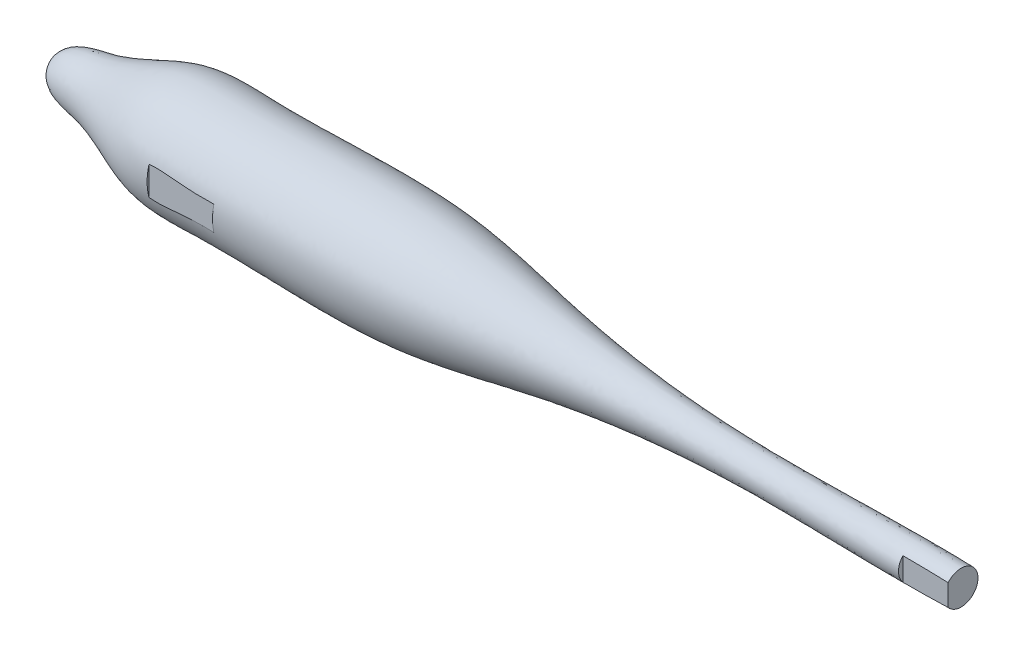
SolidWorks part; units mm, degrees
ref_plane "Front Plane" through (0, 0, 0) normal (0, 0, 1) x (1, 0, 0)
ref_plane "Top Plane" through (0, 0, 0) normal (0, 1, 0) x (1, 0, 0)
ref_plane "Right Plane" through (0, 0, 0) normal (1, 0, 0) x (0, 0, -1)
sketch "Sketch1" plane through (0, 0, 0) normal (0, 0, 1) x (1, 0, 0)
  line L1 (1400, 97.6339) -> (0, 97.6339) construction
  line L3 (0, 0) -> (1400, 0) construction
  line L5 (0, 0) -> (1400, 0)
  line L6 (1400, 0) -> (1400, 25.997)
  spline S0 degree 3 poles (0, 0) (6.0079, 35.1205) (87.5704, 35.98) (174.2855, 89.8849) (355.2298, 80.4635) (551.199, 98.1903) (802.5668, 43.0656) (1072.4121, 17.7479) (1281.1497, 28.8593) (1400, 25.997) knots 0 0 0 0 0.060909 0.147322 0.213189 0.431417 0.561861 0.75012 1 1 1 1
  point P1 (280.5824, 85.3791)
  point P5 (592.0718, 82.0807)
  point P7 (186.6455, 81.4345)
  point P9 (0, 0)
  point P11 (0, 0)
  point P14 (0, 0)
  point P16 (377.1602, -117.7023)
  dimension "D1" = 97.6339
revolve "Revolve2" add sketch "Sketch1" angle 360 about L5
ref_plane "Plane1" through (0, 0, 100) normal (0, 0, 1) x (1, 0, 0)
sketch "Sketch5" plane through (0, 0, 100) normal (0, 0, 1) x (1, 0, 0)
  line L1 (230.5342, 126.4878) -> (330.5342, 126.4878)
  line L2 (230.5342, 126.4878) -> (230.5342, -96.4704)
  line L3 (230.5342, -96.4704) -> (330.5342, -96.4704)
  line L4 (330.5342, 126.4878) -> (330.5342, -96.4704)
  line L5 (230.5342, 126.4878) -> (330.5342, -96.4704) construction
  line L6 (230.5342, -96.4704) -> (330.5342, 126.4878) construction
  point P0 (280.5342, 15.0087)
  point P5 (158.0605, -62.4764)
extrude "Cut-Extrude2" cut sketch "Sketch5" against normal blind 17
sketch "Sketch7" plane through (0, 0, 100) normal (0, 0, 1) x (1, 0, 0)
  line L1 (1330.1015, 25) -> (1400.1015, 25)
  line L2 (1330.1015, 25) -> (1330.1015, -25)
  line L3 (1330.1015, -25) -> (1400.1015, -25)
  line L4 (1400.1015, 25) -> (1400.1015, -25)
  line L5 (1330.1015, 25) -> (1400.1015, -25) construction
  line L6 (1330.1015, -25) -> (1400.1015, 25) construction
  point P0 (1365.1015, 0)
  point P5 (1365.1015, 0)
extrude "Cut-Extrude3" cut sketch "Sketch7" against normal blind 80
